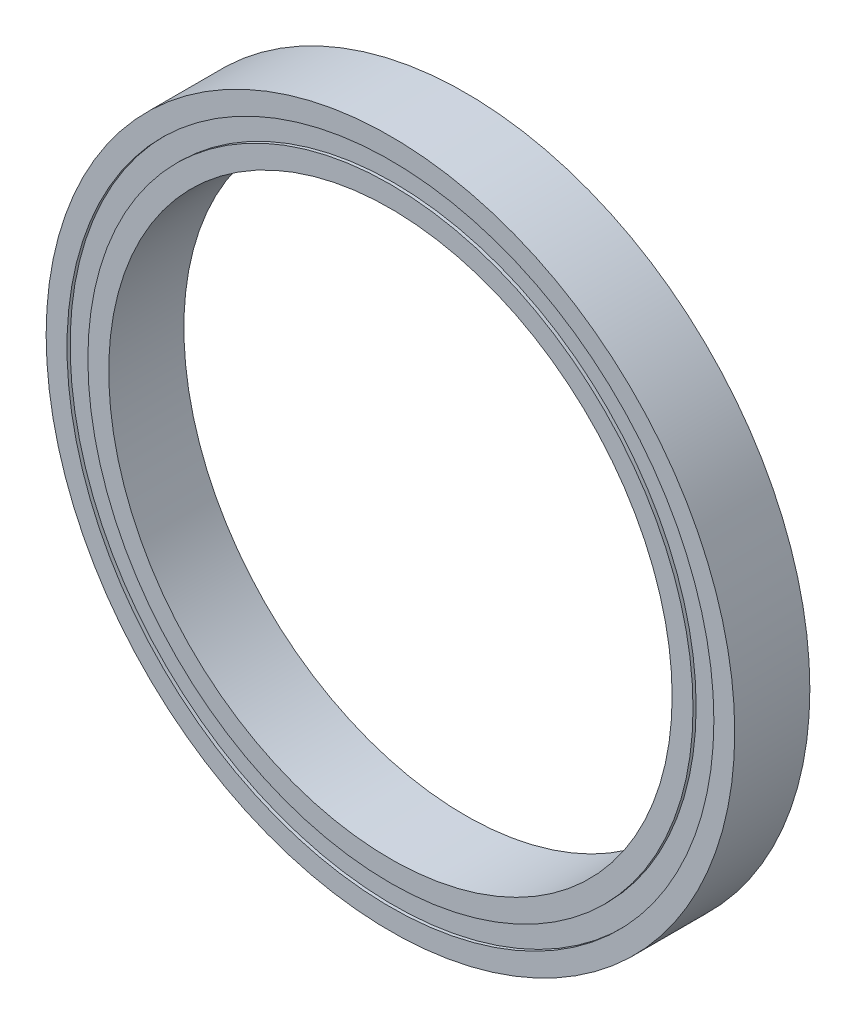
SolidWorks part; units mm, degrees
ref_plane "Front Plane" through (0, 0, 0) normal (0, 0, 1) x (1, 0, 0)
ref_plane "Top Plane" through (0, 0, 0) normal (0, 1, 0) x (1, 0, 0)
ref_plane "Right Plane" through (0, 0, 0) normal (1, 0, 0) x (0, 0, -1)
sketch "Sketch1" plane through (0, 0, 0) normal (0, 0, 1) x (1, 0, 0)
  line L0 (0, 22.5) -> (0, 24.1667) construction
  line L1 (0, 24.1667) -> (0, 25.8333) construction
  line L2 (0, 25.8333) -> (0, 27.5) construction
  circle A0 centre (0, 0) radius 22.5
  circle A1 centre (0, 0) radius 27.5
  circle A2 centre (0, 0) radius 24.1667
  circle A3 centre (0, 0) radius 25.8333
  dimension "D1" = 45
  dimension "D2" = 55
extrude "Boss-Extrude1" add sketch "Sketch1" along normal blind 3 and the other way blind 3 contours A2 A0 | A1 A3 region at (-26.7222, 0, 0) region at (-23.4831, 0, 0)
extrude "Boss-Extrude2" add sketch "Sketch1<4>" along normal blind 2.75 and the other way blind 2.75 contours A3 A2 region at (-25.1027, 0, 0)
sketch "Sketch1<4>" plane through (0, 0, 0) normal (0, 0, 1) x (1, 0, 0) same geometry as "Sketch1"
